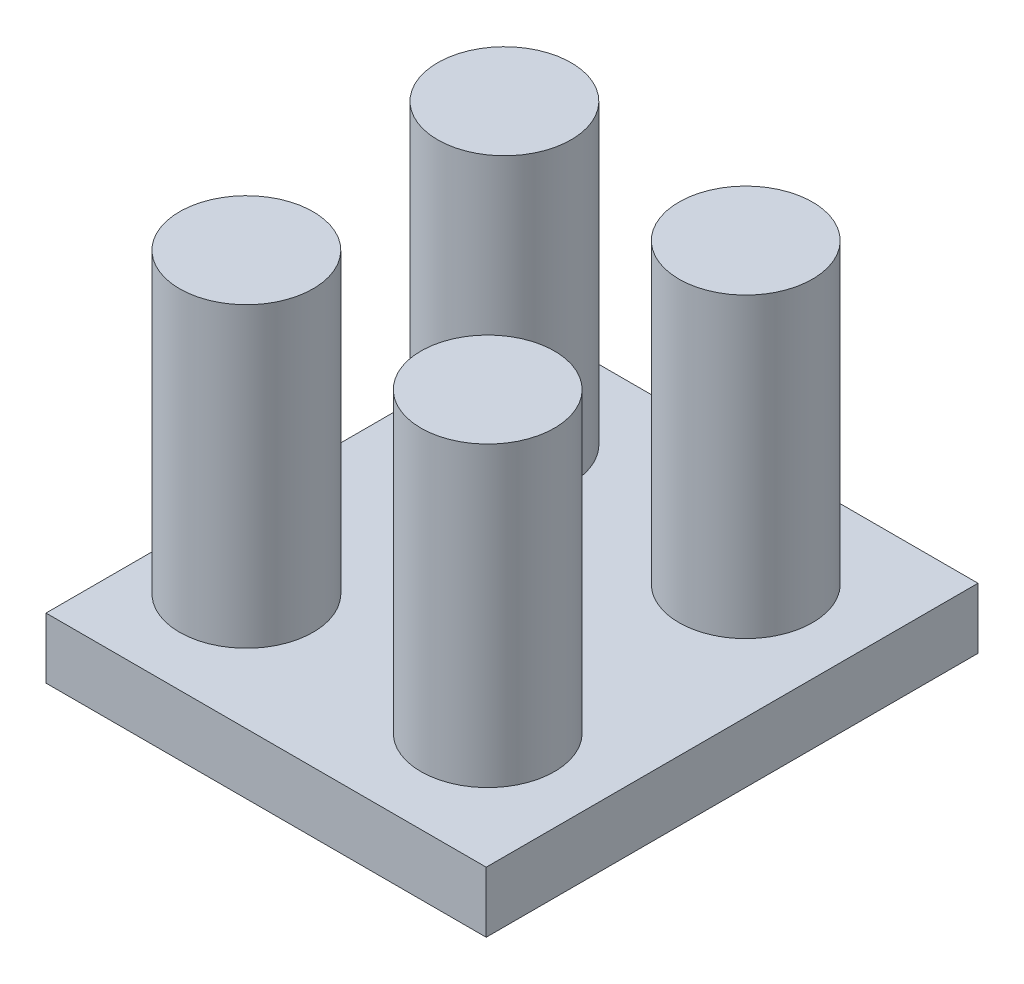
SolidWorks part; units mm, degrees
ref_plane "Front Plane" through (0, 0, 0) normal (0, 0, 1) x (1, 0, 0)
ref_plane "Top Plane" through (0, 0, 0) normal (0, 1, 0) x (1, 0, 0)
ref_plane "Right Plane" through (0, 0, 0) normal (1, 0, 0) x (0, 0, -1)
sketch "Sketch1" plane through (0, 0, 0) normal (0, 1, 0) x (1, 0, 0)
  line L0 (7.25, 0) -> (-7.25, 0) construction
  line L1 (-7.25, 8.1) -> (7.25, 8.1)
  line L2 (-7.25, 8.1) -> (-7.25, -8.1)
  line L3 (-7.25, -8.1) -> (7.25, -8.1)
  line L4 (7.25, 8.1) -> (7.25, -8.1)
  line L5 (-7.25, 8.1) -> (7.25, -8.1) construction
  line L6 (-7.25, -8.1) -> (7.25, 8.1) construction
  line L7 (7.25, -4.25) -> (3.45, -4.25) construction
  line L8 (3.45, -4.25) -> (3.45, -8.1) construction
  line L9 (3.45, -4.25) -> (-4.5, -4.25) construction
  circle A0 centre (3.45, -4.25) radius 2.2
  circle A1 centre (-4.5, -4.25) radius 2.2
  circle A2 centre (-4.5, 4.25) radius 2.2
  circle A3 centre (3.45, 4.25) radius 2.2
  point P0 (0, 0)
  dimension "D5" = 4.4
  dimension "D7" = 4.4
  dimension "D1" = 14.5
  dimension "D2" = 16.2
  dimension "D3" = 3.85
  dimension "D4" = 3.8
  dimension "D6" = 7.95
extrude "Boss-Extrude2" add sketch "Sketch1" along normal blind 2
sketch "Sketch2" plane through (0, 2, 0) normal (0, 1, 0) x (1, 0, 0)
  circle A0 centre (3.45, 4.25) radius 2.2
  circle A1 centre (-4.5, 4.25) radius 2.2
  circle A2 centre (3.45, -4.25) radius 2.2
  circle A3 centre (-4.5, -4.25) radius 2.2
extrude "Boss-Extrude3" add sketch "Sketch2" along normal blind 9.8 and the other way up to surface (2 mm away) separate body other way up to face at (0, 0, 0)
